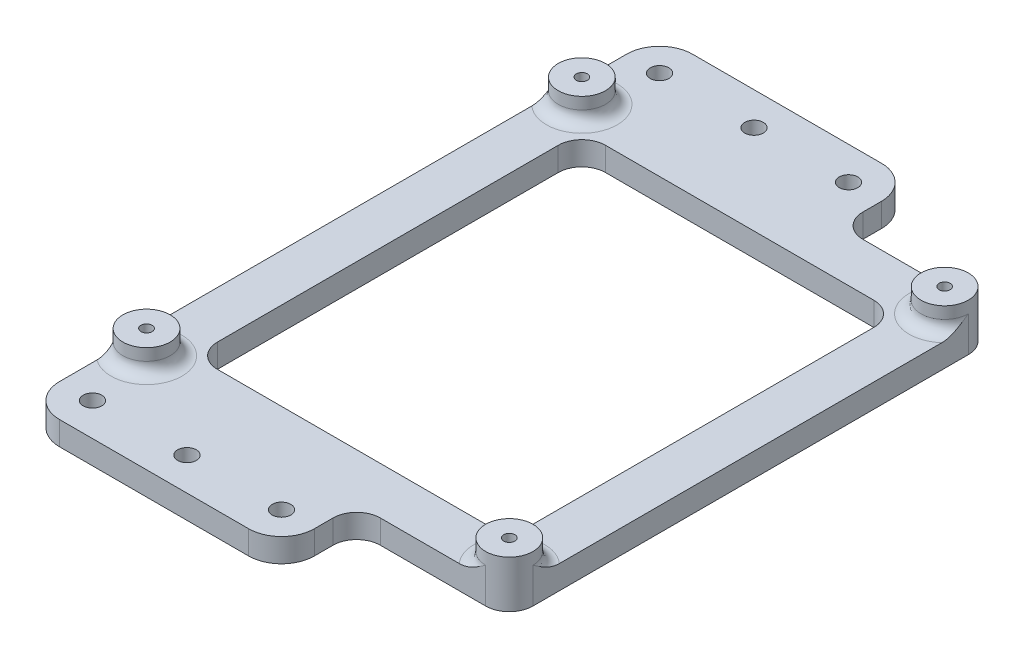
SolidWorks part; units mm, degrees
ref_plane "Front Plane" through (0, 0, 0) normal (0, 0, 1) x (1, 0, 0)
ref_plane "Top Plane" through (0, 0, 0) normal (0, 1, 0) x (1, 0, 0)
ref_plane "Right Plane" through (0, 0, 0) normal (1, 0, 0) x (0, 0, -1)
sketch "Sketch1" plane through (0, 0, 0) normal (0, 1, 0) x (1, 0, 0)
  line L0 (-27.55, 32.425) -> (27.55, 32.425)
  line L1 (-24.375, -29.25) -> (-21.2, -29.25) construction
  line L2 (-24.375, -29.25) -> (-24.375, 29.25) construction
  line L3 (-24.375, 29.25) -> (24.375, 29.25) construction
  line L4 (24.375, -29.25) -> (24.375, 29.25) construction
  line L5 (-24.375, -29.25) -> (-21.2, -25.44) construction
  line L6 (-24.375, 29.25) -> (21.7292, -26.075) construction
  line L7 (27.55, -32.425) -> (27.55, 32.425)
  line L8 (-27.55, -32.425) -> (-21.2, -32.425)
  line L9 (-27.55, -32.425) -> (-27.55, 32.425)
  line L10 (-21.2, 26.075) -> (21.2, 26.075)
  line L11 (21.2, -26.075) -> (21.2, 26.075)
  line L12 (-21.2, -26.075) -> (-21.7292, -26.075) construction
  line L13 (-21.2, -26.075) -> (-21.2, 26.075)
  line L14 (-21.2, -26.075) -> (-21.2, -32.425) construction
  line L15 (21.2, -26.075) -> (21.2, -32.425) construction
  line L16 (-21.7292, -26.075) -> (21.7292, -26.075) construction
  line L17 (21.7292, -26.075) -> (21.2, -26.075) construction
  line L18 (-21.2, -26.075) -> (21.2, -26.075) construction
  line L19 (-21.2, -29.25) -> (21.2, -29.25) construction
  line L20 (21.2, -29.25) -> (24.375, -29.25) construction
  line L21 (-24.375, -29.25) -> (24.375, -29.25) construction
  line L22 (-21.2, -32.425) -> (21.2, -32.425) construction
  line L23 (21.2, -32.425) -> (27.55, -32.425)
  line L24 (-27.55, -32.425) -> (27.55, -32.425) construction
  line L25 (-21.7292, -26.075) -> (0, 0) construction
  line L26 (0, 0) -> (24.375, 29.25) construction
  line L27 (-21.2, -25.44) -> (-21.7292, -26.075) construction
  line L28 (21.7292, -26.075) -> (21.2, -25.44) construction
  line L29 (21.2, -25.44) -> (24.375, -29.25) construction
  line L30 (21.2, -26.075) -> (-21.2, -26.075)
  line L31 (-21.2, -32.425) -> (21.2, -32.425)
  circle A0 centre (-24.375, 29.25) radius 0.75
  circle A1 centre (24.375, 29.25) radius 0.75
  circle A2 centre (24.375, -29.25) radius 0.75
  circle A3 centre (-24.375, -29.25) radius 0.75
  point P0 (0, 0)
  dimension "D3" = 1.5
  dimension "D1" = 48.75
  dimension "D2" = 58.5
  dimension "D4" = 3.175
  dimension "D5" = 3.175
extrude "Boss-Extrude1" add sketch "Sketch1" along normal blind 3.175
fillet "Fillet1" radius 3.175 8 edges at (21.2, 1.5875, -26.075) (-21.2, 1.5875, -26.075) (-27.55, 1.5875, -32.425) (27.55, 1.5875, -32.425) (27.55, 1.5875, 32.425) (-27.55, 1.5875, 32.425) (-21.2, 1.5875, 26.075) (21.2, 1.5875, 26.075)
sketch "Sketch2" plane through (0, 3.175, 0) normal (0, 1, 0) x (1, 0, 0)
  circle A0 centre (-24.375, 29.25) radius 0.75 construction
  circle A1 centre (-24.375, 29.25) radius 0.75
  circle A2 centre (-24.375, 29.25) radius 3.175
  arc A3 (-24.375, 32.425) -> (-27.55, 29.25) centre (-24.375, 29.25) ccw construction
extrude "Boss-Extrude2" add sketch "Sketch2" along normal blind 3.175
mirror "Mirror3" about plane through (0, 0, 0) normal (1, 0, 0) of "Boss-Extrude2"
mirror "Mirror4" about plane through (0, 0, 0) normal (0, 0, 1) of "Mirror3", "Boss-Extrude2"
sketch "Sketch4" plane through (0, 0, 0) normal (0, 1, 0) x (1, 0, 0)
  line L0 (-22.7875, 42.525) -> (2.6125, 42.525)
  line L1 (-22.7875, -38.1) -> (2.6125, -38.1) construction
  line L2 (-22.7875, -38.1) -> (-22.7875, 38.1) construction
  line L3 (-22.7875, 38.1) -> (2.6125, 38.1) construction
  line L4 (2.6125, -38.1) -> (2.6125, 38.1) construction
  line L5 (-22.7875, -38.1) -> (2.6125, 38.1) construction
  line L6 (-22.7875, 38.1) -> (2.6125, -38.1) construction
  line L7 (-27.2125, 38.1) -> (-27.2125, 32.425)
  line L8 (24.375, 32.425) -> (-24.375, 32.425) construction
  line L9 (-27.2125, 32.425) -> (7.0375, 32.425) construction
  line L10 (7.0375, 32.425) -> (7.0375, 38.1)
  line L11 (-27.55, 29.25) -> (-27.55, -29.25) construction
  line L12 (-27.2125, 32.425) -> (-27.2125, 30.0437)
  line L13 (-27.2125, 30.0437) -> (7.0375, 30.0437)
  line L14 (7.0375, 30.0437) -> (7.0375, 32.425)
  circle A0 centre (-22.7875, 38.1) radius 1.25
  circle A1 centre (-10.0875, 38.1) radius 1.25
  circle A2 centre (2.6125, 38.1) radius 1.25
  arc A3 (-27.2125, 38.1) -> (-22.7875, 42.525) centre (-22.7875, 38.1) cw
  arc A4 (7.0375, 38.1) -> (2.6125, 42.525) centre (2.6125, 38.1) ccw
  point P0 (-10.0875, 0)
  dimension "D3" = 2.5
  dimension "D4" = 3.175
  dimension "D1" = 25.4
  dimension "D2" = 76.2
  dimension "D5" = 4.7625
  dimension "D6" = 2.3813
extrude "Boss-Extrude3" add sketch "Sketch4" along normal up to surface (3.175 mm away) up to face at (0, 3.175, 0)
mirror "Mirror9" about plane through (0, 0, 0) normal (0, 0, 1) of "Boss-Extrude3"
fillet "Fillet3" radius 3.175 4 edges at (7.0375, 1.5875, -32.425) (7.0375, 1.5875, 32.425) (-27.2125, 1.5875, 30.6745) (-27.2125, 1.5875, -30.6745)
fillet "Fillet2" radius 1.5875 4 edges at (-21.2425, 3.175, -28.7324) (-21.2425, 3.175, 28.7324) (22.1299, 3.175, 27.0049) (22.1299, 3.175, -27.0049)
sketch "Sketch5" plane through (0, 0, 0) normal (0, -1, 0) x (1, 0, 0)
  line L0 (21.2, 22.9) -> (21.2, -22.9) construction
  line L1 (18.025, -26.075) -> (-18.025, -26.075) construction
  line L2 (-21.2, -22.9) -> (-21.2, 22.9) construction
  line L3 (-18.025, 26.075) -> (18.025, 26.075) construction
  line L4 (21.2, 22.9) -> (21.2, -22.9)
  line L5 (18.025, -26.075) -> (-18.025, -26.075)
  line L6 (-21.2, -22.9) -> (-21.2, 22.9)
  line L7 (-18.025, 26.075) -> (18.025, 26.075)
  arc A0 (21.2, 22.9) -> (18.025, 26.075) centre (18.025, 22.9) ccw construction
  arc A1 (18.025, -26.075) -> (21.2, -22.9) centre (18.025, -22.9) ccw construction
  arc A2 (-21.2, -22.9) -> (-18.025, -26.075) centre (-18.025, -22.9) ccw construction
  arc A3 (-18.025, 26.075) -> (-21.2, 22.9) centre (-18.025, 22.9) ccw construction
  arc A4 (21.2, 22.9) -> (18.025, 26.075) centre (18.025, 22.9) ccw
  arc A5 (18.025, -26.075) -> (21.2, -22.9) centre (18.025, -22.9) ccw
  arc A6 (-21.2, -22.9) -> (-18.025, -26.075) centre (-18.025, -22.9) ccw
  arc A7 (-18.025, 26.075) -> (-21.2, 22.9) centre (-18.025, 22.9) ccw
extrude "Boss-Extrude4" [suppressed] add sketch "Sketch5" against normal up to surface (3.175 mm away)
